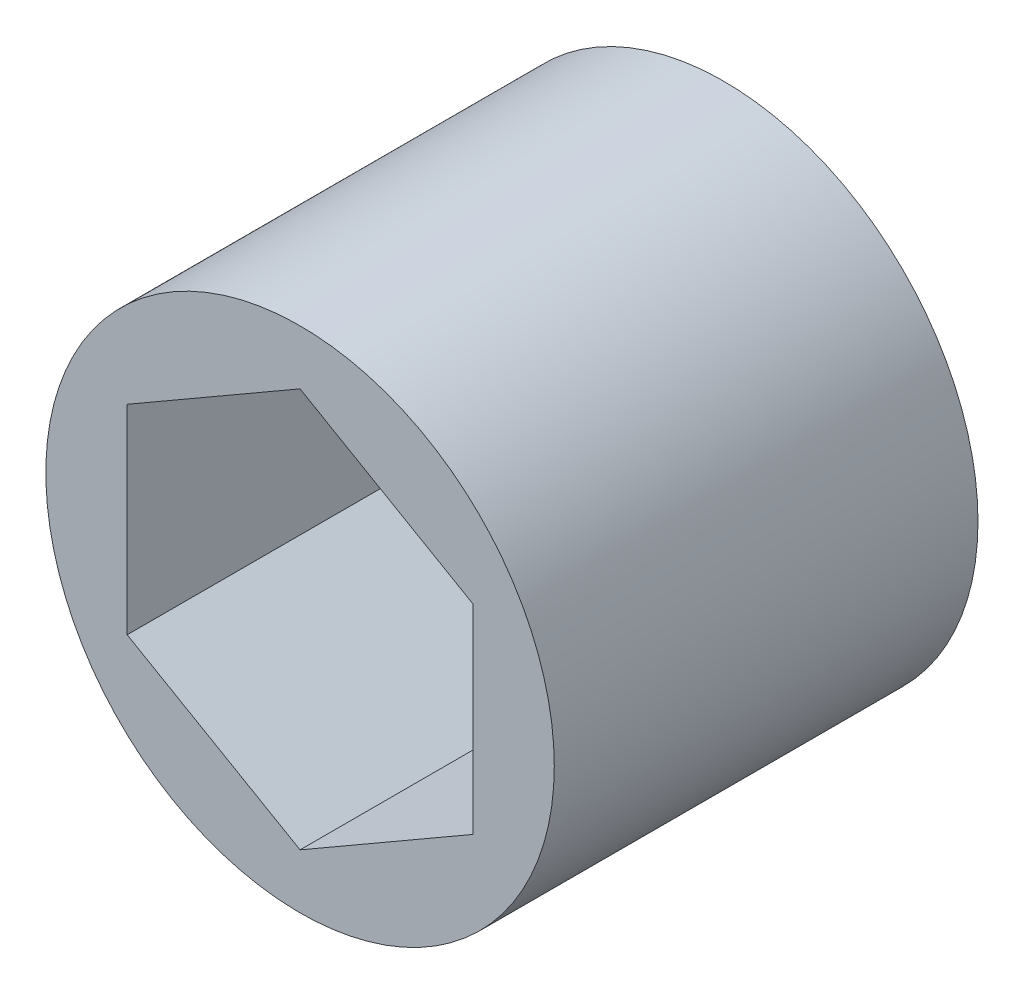
SolidWorks part; units mm, degrees
material "PET"
ref_plane "Front Plane" through (0, 0, 0) normal (0, 0, 1) x (1, 0, 0)
ref_plane "Top Plane" through (0, 0, 0) normal (0, 1, 0) x (1, 0, 0)
ref_plane "Right Plane" through (0, 0, 0) normal (1, 0, 0) x (0, 0, -1)
sketch "Sketch1" plane through (0, 0, 0) normal (0, 0, 1) x (1, 0, 0)
  line L1 (0, 7.479) -> (-6.477, 3.7395)
  line L2 (-6.477, 3.7395) -> (-6.477, -3.7395)
  line L3 (-6.477, -3.7395) -> (0, -7.479)
  line L4 (0, -7.479) -> (6.477, -3.7395)
  line L5 (6.477, -3.7395) -> (6.477, 3.7395)
  line L6 (6.477, 3.7395) -> (0, 7.479)
  circle A0 centre (0, 0) radius 9.525
  circle A1 centre (0, 0) radius 6.477 construction
  dimension "D1" = 12.954
  dimension "D2" = 19.05
extrude "Boss-Extrude1" add sketch "Sketch1" along normal mid plane 15.875
